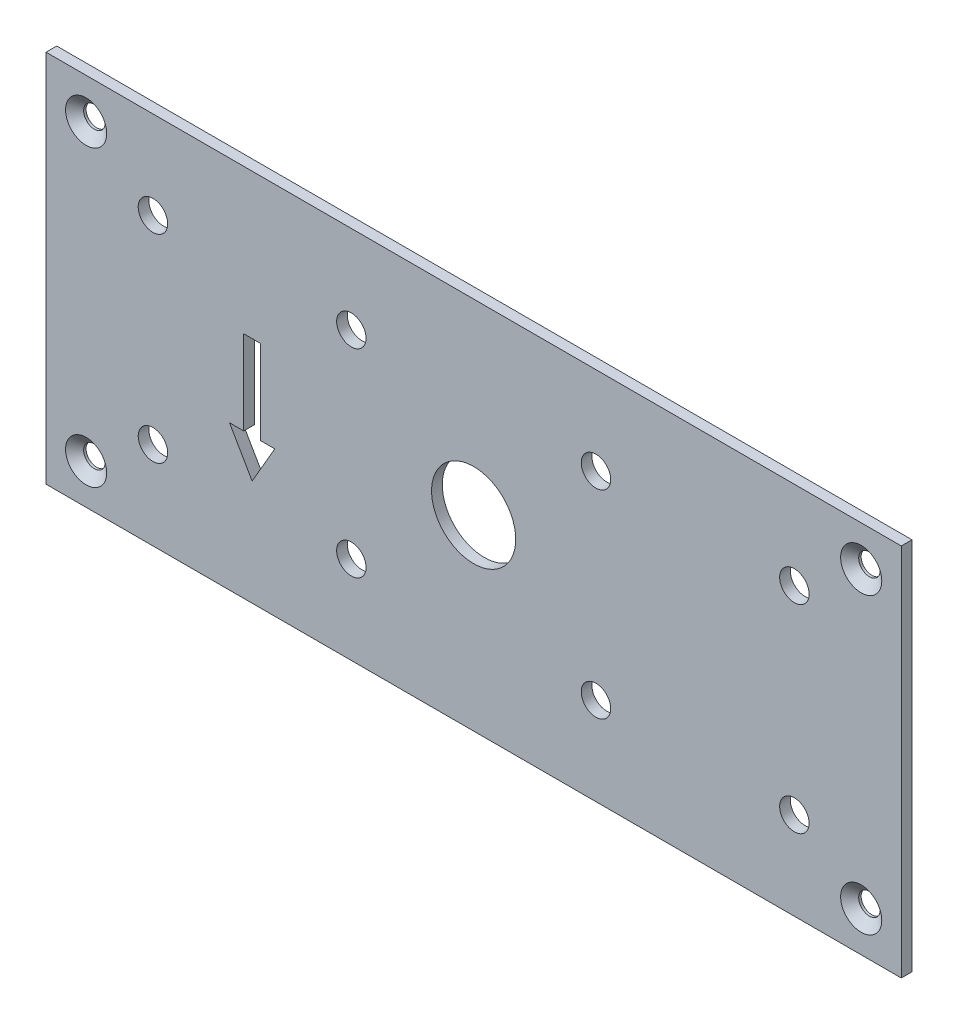
SolidWorks part; units mm, degrees
ref_plane "Front Plane" through (0, 0, 0) normal (0, 0, 1) x (1, 0, 0)
ref_plane "Top Plane" through (0, 0, 0) normal (0, 1, 0) x (1, 0, 0)
ref_plane "Right Plane" through (0, 0, 0) normal (1, 0, 0) x (0, 0, -1)
sketch "Sketch2" plane through (0, 0, 0) normal (0, 0, 1) x (1, 0, 0)
  line L0 (-29.06, 23.57) -> (-76.2, 23.57) construction
  line L1 (-101.6, -44.45) -> (101.6, -44.45)
  line L2 (-101.6, -44.45) -> (-101.6, 44.45)
  line L3 (-101.6, 44.45) -> (101.6, 44.45)
  line L4 (101.6, -44.45) -> (101.6, 44.45)
  line L5 (-101.6, -44.45) -> (101.6, 44.45) construction
  line L6 (-101.6, 44.45) -> (101.6, -44.45) construction
  line L7 (-76.2, 23.57) -> (-76.2, -23.57) construction
  line L8 (-76.2, -23.57) -> (-29.06, -23.57) construction
  line L9 (-29.06, -23.57) -> (-29.06, 23.57) construction
  line L10 (-76.2, 0) -> (-101.6, 0) construction
  line L12 (29.06, -23.57) -> (76.2, -23.57) construction
  line L13 (76.2, -23.57) -> (76.2, 23.57) construction
  line L14 (76.2, 23.57) -> (29.06, 23.57) construction
  line L15 (29.06, 23.57) -> (29.06, -23.57) construction
  line L17 (76.2, 0) -> (101.6, 0) construction
  circle A11 centre (-76.2, 23.57) radius 3.5
  circle A12 centre (-29.06, 23.57) radius 3.5
  circle A13 centre (-29.06, -23.57) radius 3.5
  circle A14 centre (-76.2, -23.57) radius 3.5
  circle A15 centre (29.06, -23.57) radius 3.5
  circle A16 centre (76.2, -23.57) radius 3.5
  circle A17 centre (76.2, 23.57) radius 3.5
  circle A18 centre (29.06, 23.57) radius 3.5
  circle A19 centre (0, 0) radius 10
  point P0 (0, 0)
  point P17 (101.6, 0)
  point P23 (-101.6, 0)
  dimension "D3" = 7
  dimension "D6" = 20
  dimension "D1" = 47.14
  dimension "D2" = 88.9
  dimension "D4" = 203.2
  dimension "D5" = 25.4
extrude "Boss-Extrude1" add sketch "Sketch2" along normal mid plane 2.54
sketch "Sketch3" plane through (0, 0, 1.27) normal (0, 0, 1) x (1, 0, 0)
  line L0 (-101.6, 34.925) -> (-92.075, 34.925) construction
  line L1 (-101.6, 44.45) -> (-101.6, -44.45) construction
  line L2 (-92.075, 34.925) -> (-92.075, 44.45) construction
  line L3 (101.6, 44.45) -> (-101.6, 44.45) construction
  line L4 (92.075, 44.45) -> (92.075, 34.925) construction
  line L5 (92.075, 34.925) -> (101.6, 34.925) construction
  line L6 (101.6, -44.45) -> (101.6, 44.45) construction
  line L7 (92.075, -44.45) -> (92.075, -34.925) construction
  line L8 (-101.6, -44.45) -> (101.6, -44.45) construction
  line L9 (92.075, -34.925) -> (101.6, -34.925) construction
  line L10 (-92.075, -44.45) -> (-92.075, -34.925) construction
  line L11 (-92.075, -34.925) -> (-101.6, -34.925) construction
  circle A0 centre (-92.075, 34.925) radius 2.5527
  circle A1 centre (-92.075, -34.925) radius 2.5527
  circle A2 centre (92.075, -34.925) radius 2.5527
  circle A3 centre (92.075, 34.925) radius 2.5527
  dimension "D2" = 5.1054
  dimension "D1" = 9.525
extrude "Cut-Extrude1" cut sketch "Sketch3" against normal through all
sketch "Sketch4" plane through (0, 0, 1.27) normal (0, 0, 1) x (1, 0, 0)
  line L0 (-76.2, 23.57) -> (-29.06, -23.57) construction
  line L1 (-54.63, -10) -> (-58.0088, -10)
  line L2 (-54.63, -10) -> (-50.63, -10)
  line L3 (-54.63, -10) -> (-54.63, 10)
  line L4 (-54.63, 10) -> (-50.63, 10)
  line L5 (-50.63, -10) -> (-50.63, 10)
  line L6 (-54.63, -10) -> (-50.63, 10) construction
  line L7 (-54.63, 10) -> (-50.63, -10) construction
  line L8 (-58.0088, -10) -> (-52.63, -19.3163)
  line L9 (-52.63, -19.3163) -> (-47.2512, -10)
  line L10 (-50.63, -10) -> (-47.2512, -10)
  point P3 (-52.63, 0)
  dimension "D1" = 4
  dimension "D2" = 20
  dimension "D3" = 60
extrude "Cut-Extrude2" cut sketch "Sketch4" against normal through all both and the other way through all contours L10 L2 L1 L8 L9 | L2 L5 L4 L3 region at (-52.63, -13.1054, 1.27) region at (-52.63, 0, 1.27)
hole_wizard "CSK for #10 Flat Head Machine Screw (100)1" positions "Sketch5" profile "Sketch6" countersink size "#10" standard "ANSI Inch" end condition through all
sketch "Sketch5" plane through (0, 0, 1.27) normal (0, 0, 1) x (1, 0, 0)
  point P0 (-92.075, 34.925)
  point P3 (-92.075, -34.925)
  point P6 (92.075, -34.925)
  point P9 (92.075, 34.925)
sketch "Sketch6" plane through (-92.075, 34.925, 1.27) normal (1, 0, 0) x (0, -1, 0)
  line L0 (0, 0) -> (0, 2.54)
  line L1 (0, 2.54) -> (2.5527, 2.54)
  line L2 (2.5527, 2.54) -> (2.5527, 1.9608)
  line L3 (2.5527, 1.9608) -> (4.8895, 0)
  line L5 (4.8895, 0) -> (0, 0)
  line L6 (-2.5527, 1.9608) -> (-4.8895, 0) construction
  line L11 (0, -6.35) -> (0, 107.95) construction
  dimension "Thru Hole Dia." = 5.1054
  dimension "Thru Hole Depth" = 2.54
  dimension "Near C'Sink Dia." = 9.779
  dimension "Near C'Sink Angle" = 100
